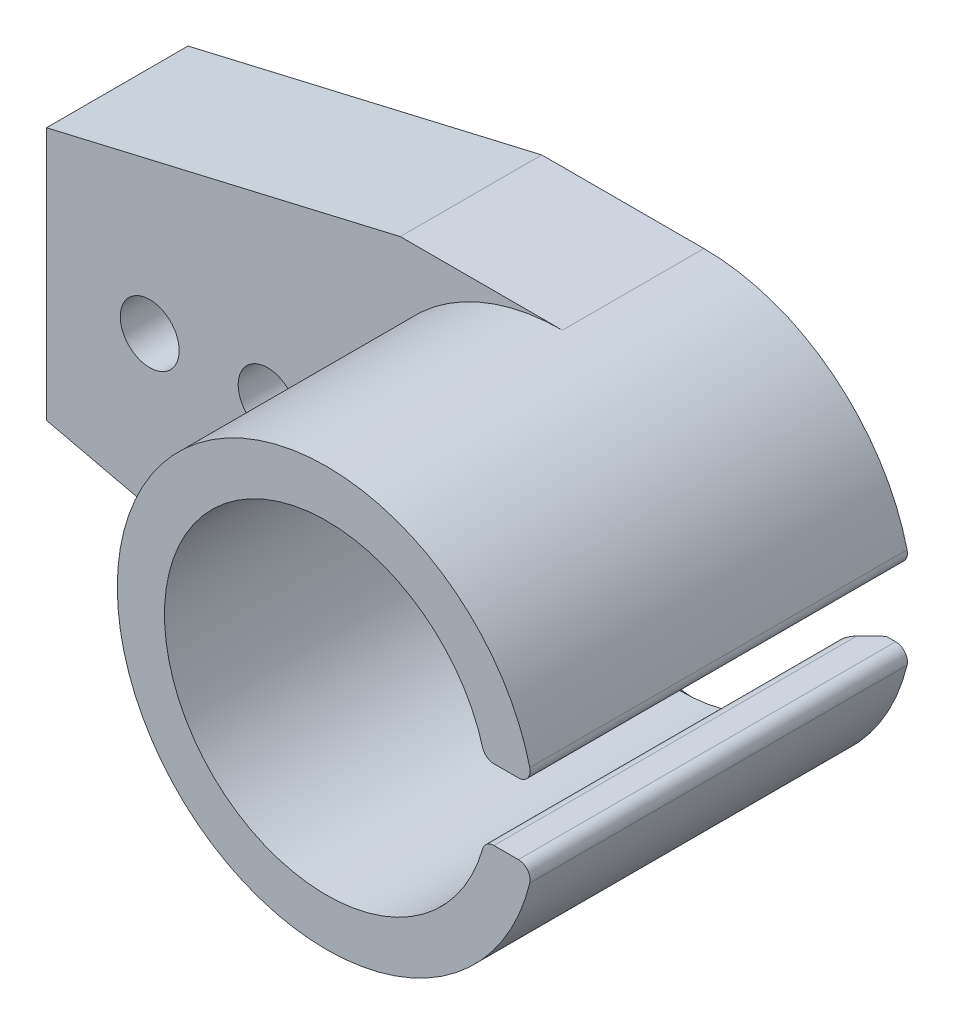
SolidWorks part; units mm, degrees
ref_plane "Plan de face" through (0, 0, 0) normal (0, 0, 1) x (1, 0, 0)
ref_plane "Plan de dessus" through (0, 0, 0) normal (0, 1, 0) x (1, 0, 0)
ref_plane "Plan de droite" through (0, 0, 0) normal (1, 0, 0) x (0, 0, -1)
sketch "Esquisse1" plane through (0, 0, 0) normal (0, 0, 1) x (1, 0, 0)
  line L0 (0, 0) -> (13.75, 0) construction
  line L1 (0, 3) -> (21.7672, 3) construction
  line L2 (0, -3) -> (21.7672, -3) construction
  line L3 (13.4187, 3) -> (17.4946, 3)
  line L4 (17.4946, -3) -> (13.4187, -3)
  line L5 (0, 0) -> (0, 17.75) construction
  line L6 (0, -17.75) -> (-43.75, -17.75)
  line L7 (-43.75, -17.75) -> (-43.75, 17.75)
  line L8 (-43.75, 17.75) -> (0, 17.75)
  circle A0 centre (0, 0) radius 13.75 construction
  arc A1 (13.4187, 3) -> (13.4187, -3) centre (0, 0) ccw
  arc A3 (17.4946, 3) -> (0, 17.75) centre (0, 0) ccw
  arc A4 (17.4946, -3) -> (0, -17.75) centre (0, 0) cw
  circle A5 centre (-35, 0) radius 2.5
  circle A6 centre (-25, 0) radius 2.5
  point P18 (-13.75, 0)
  dimension "D1" = 27.5
  dimension "D2" = 6
  dimension "D3" = 30
  dimension "D4" = 4
  dimension "D6" = 5
  dimension "D5" = 10
  dimension "D7" = 25
extrude "Boss.-Extru.1" add sketch "Esquisse1" along normal blind 32
chamfer "Chanfrein1" distance 2 angle 45 1 edges at (-13.75, 0, 0)
fillet "Congé2" radius 1 4 edges at (17.4946, -3, 16) (17.4946, 3, 16) (13.4187, -3, 17) (13.4187, 3, 17)
sketch "Esquisse2" plane through (0, 0, 0) normal (0, 0, -1) x (-1, 0, 0)
  line L0 (43.75, 10.1) -> (25, 10.1)
  line L1 (43.75, 17.75) -> (43.75, -17.75) construction
  line L2 (25, -10.1) -> (43.75, -10.1)
  line L3 (43.75, -10.1) -> (43.75, 10.1)
  arc A0 (25, 10.1) -> (25, -10.1) centre (25, 0) ccw
  circle A1 centre (25, 0) radius 2.5 construction
  dimension "D1" = 20.2
extrude "Enlèv. mat.-Extru.1" cut sketch "Esquisse2" against normal blind 2
sketch "Esquisse3" plane through (0, 0, 32) normal (0, 0, 1) x (1, 0, 0)
  line L0 (0, 17.75) -> (-43.75, 17.75) construction
  line L1 (0, 17.75) -> (-43.75, 17.75)
  line L2 (-43.75, 17.75) -> (-43.75, -17.75)
  line L3 (-43.75, -17.75) -> (0, -17.75)
  line L4 (-43.75, 17.75) -> (-43.75, -17.75) construction
  arc A1 (0, 17.75) -> (0, -17.75) centre (0, 0) ccw
  arc A2 (17.2364, 4.2388) -> (0, 17.75) centre (0, 0) ccw construction
  arc A3 (0, -17.75) -> (17.2364, -4.2388) centre (0, 0) ccw construction
extrude "Enlèv. mat.-Extru.2" cut sketch "Esquisse3" against normal blind 20
sketch "Esquisse5" plane through (0, 0, 12) normal (0, 0, 1) x (1, 0, 0)
  line L0 (-13.75, 17.75) -> (-43.75, 10.75)
  line L1 (0, 17.75) -> (-43.75, 17.75) construction
  line L2 (-43.75, 17.75) -> (-43.75, -17.75) construction
  line L3 (-43.75, 10.75) -> (-43.75, 17.75)
  line L4 (-43.75, 17.75) -> (-13.75, 17.75)
  line L5 (-43.75, 0) -> (0, 0) construction
  line L6 (-43.75, -17.75) -> (-13.75, -17.75)
  line L7 (-43.75, -10.75) -> (-43.75, -17.75)
  line L8 (-13.75, -17.75) -> (-43.75, -10.75)
  dimension "D1" = 7
  dimension "D2" = 30
extrude "Enlèv. mat.-Extru.3" cut sketch "Esquisse5" against normal through all
